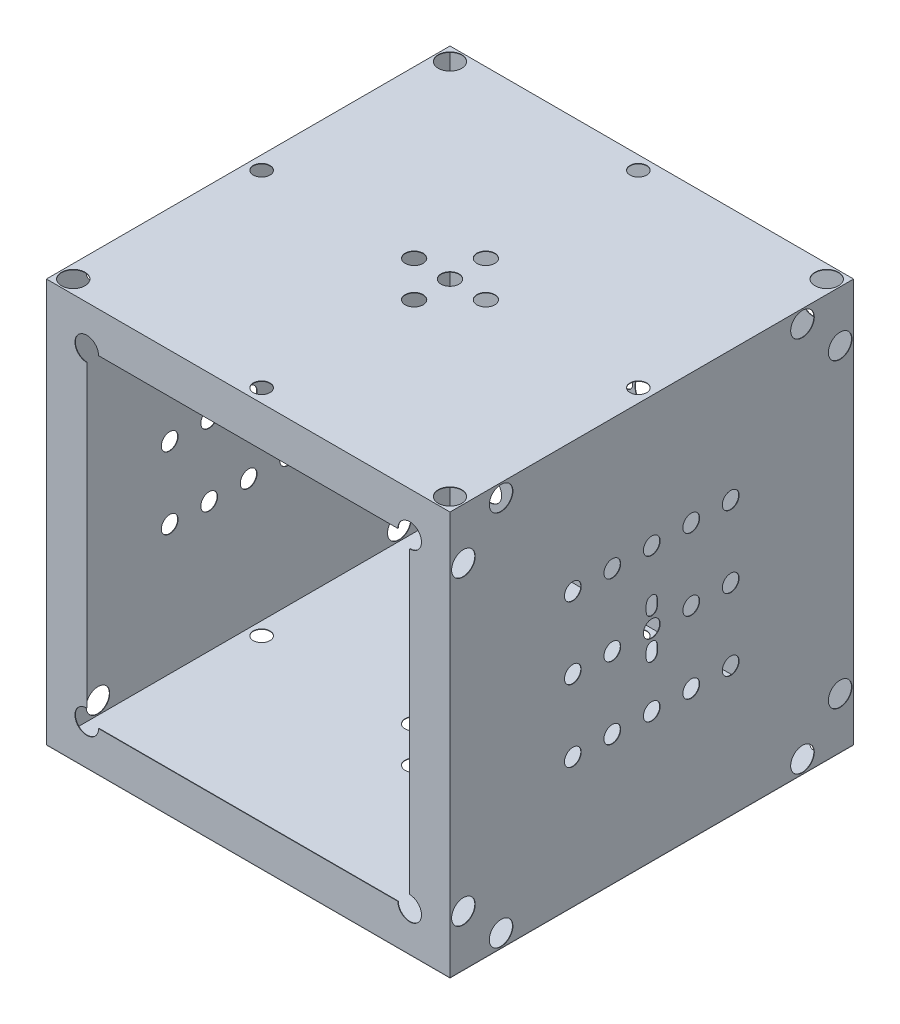
SolidWorks part; units mm, degrees
ref_plane "Front" through (0, 0, 0) normal (0, 0, 1) x (1, 0, 0)
ref_plane "Top" through (0, 0, 0) normal (0, 1, 0) x (1, 0, 0)
ref_plane "Right" through (0, 0, 0) normal (1, 0, 0) x (0, 0, -1)
sketch "Sketch1" plane through (0, 0, 0) normal (0, 1, 0) x (1, 0, 0)
  line L1 (-1124.8, 1124.8) -> (1124.8, 1124.8)
  line L2 (-1124.8, 1124.8) -> (-1124.8, -1124.8)
  line L3 (-1124.8, -1124.8) -> (1124.8, -1124.8)
  line L4 (1124.8, 1124.8) -> (1124.8, -1124.8)
  line L5 (-1124.8, 1124.8) -> (1124.8, -1124.8) construction
  line L6 (-1124.8, -1124.8) -> (1124.8, 1124.8) construction
  point P0 (0, 0)
  dimension "D1" = 2249.6
  dimension "D2" = 2249.6
extrude "Boss-Extrude1" add sketch "Sketch1" along normal blind 2249.6
shell "Shell1" thickness 2.4 removed face at (0, 1124.8, 1124.8)
sketch "Sketch2" plane through (0, 0, 1124.8) normal (0, 0, 1) x (1, 0, 0)
  line L0 (0, 2249.6) -> (0, 0) construction
  line L1 (-1124.8, 2249.6) -> (1124.8, 2249.6)
  line L2 (-1124.8, 2249.6) -> (-1124.8, 0)
  line L3 (-1124.8, 0) -> (1124.8, 0)
  line L4 (1124.8, 2249.6) -> (1124.8, 0)
  line L5 (1124.8, 1124.8) -> (-1124.8, 1124.8) construction
  line L7 (-900, 2024.8) -> (900, 2024.8)
  line L8 (-900, 2024.8) -> (-900, 224.8)
  line L9 (-900, 224.8) -> (900, 224.8)
  line L10 (900, 2024.8) -> (900, 224.8)
  line L11 (-900, 2024.8) -> (900, 224.8) construction
  line L12 (-900, 224.8) -> (900, 2024.8) construction
  point P11 (0, 1124.8)
  dimension "D1" = 1800
  dimension "D2" = 1800
extrude "Boss-Extrude3" add sketch "Sketch2" against normal blind 2.4
sketch "Sketch3" plane through (0, 2249.6, 0) normal (0, 1, 0) x (1, 0, 0)
  line L0 (-1124.8, 0) -> (1124.8, 0) construction
  line L1 (-1124.8, 1124.8) -> (-1124.8, -1124.8) construction
  line L2 (1124.8, -1124.8) -> (1124.8, 1124.8) construction
  line L3 (0, 1124.8) -> (0, -1124.8) construction
  line L4 (1124.8, 1124.8) -> (-1124.8, 1124.8) construction
  line L5 (-1124.8, -1124.8) -> (1124.8, -1124.8) construction
  line L6 (-1124.8, 1124.8) -> (0, 0) construction
  line L7 (0, 0) -> (-200, 0) construction
  circle A0 centre (0, 0) radius 49.85
  circle A1 centre (-200, 0) radius 49.85
  circle A2 centre (-1050, 0) radius 46.75
  circle A3 centre (-1050, 1050) radius 65.8
  circle A4 centre (1050, 1050) radius 65.8
  circle A5 centre (200, 0) radius 49.85
  circle A6 centre (1050, 0) radius 46.75
  circle A7 centre (-1050, -1050) radius 65.8
  circle A8 centre (0, -1050) radius 46.75
  circle A9 centre (0, -200) radius 49.85
  circle A10 centre (0, 200) radius 49.85
  circle A11 centre (0, 1050) radius 46.75
  circle A12 centre (1050, -1050) radius 65.8
  dimension "D1" = 99.7
  dimension "D4" = 93.5
  dimension "D6" = 131.6
  dimension "D3" = 200
  dimension "D5" = 1050
  dimension "D7" = 1050
  dimension "D2" = 2
extrude "Cut-Extrude1" cut sketch "Sketch3" against normal through all
sketch "Sketch4" plane through (-1124.8, 0, 0) normal (-1, 0, 0) x (0, 0, 1)
  line L0 (0, 2249.6) -> (0, 0) construction
  line L1 (-1124.8, 2249.6) -> (1124.8, 2249.6) construction
  line L2 (-1124.8, 1124.8) -> (1124.8, 1124.8) construction
  line L3 (-1124.8, 2249.6) -> (-1124.8, 0) construction
  line L4 (1124.8, 2249.6) -> (1124.8, 0) construction
  line L5 (-1124.8, 2249.6) -> (0, 1124.8) construction
  line L6 (0, 1124.8) -> (-220, 1124.8) construction
  line L7 (0, 1124.8) -> (0, 1524.8) construction
  line L8 (-440, 1124.8) -> (-440, 1524.8) construction
  line L9 (0, 1254.8) -> (0, 1217.3) construction
  line L10 (30.9, 1254.8) -> (30.9, 1217.3)
  line L11 (-30.9, 1254.8) -> (-30.9, 1217.3)
  line L12 (0, 994.8) -> (0, 1032.3) construction
  line L13 (30.9, 994.8) -> (30.9, 1032.3)
  line L14 (-30.9, 994.8) -> (-30.9, 1032.3)
  circle A0 centre (0, 1124.8) radius 46.75
  circle A1 centre (-220, 1124.8) radius 46.75
  circle A2 centre (-440, 1124.8) radius 46.75
  circle A6 centre (-440, 1524.8) radius 46.75 [skipped]
  circle A7 centre (-220, 1524.8) radius 46.75 [skipped]
  circle A8 centre (0, 1524.8) radius 46.75 [skipped]
  circle A9 centre (220, 1124.8) radius 46.75
  circle A10 centre (440, 1124.8) radius 46.75
  circle A11 centre (-440, 1524.8) radius 46.75
  circle A12 centre (-220, 1524.8) radius 46.75
  circle A13 centre (0, 1524.8) radius 46.75
  circle A14 centre (220, 1524.8) radius 46.75
  circle A15 centre (440, 1524.8) radius 46.75
  circle A16 centre (440, 724.8) radius 46.75
  circle A17 centre (220, 724.8) radius 46.75
  circle A18 centre (0, 724.8) radius 46.75
  circle A19 centre (-220, 724.8) radius 46.75
  circle A20 centre (-440, 724.8) radius 46.75
  arc A21 (30.9, 1254.8) -> (-30.9, 1254.8) centre (0, 1254.8) ccw
  arc A22 (-30.9, 1217.3) -> (30.9, 1217.3) centre (0, 1217.3) ccw
  arc A23 (30.9, 994.8) -> (-30.9, 994.8) centre (0, 994.8) cw
  arc A24 (-30.9, 1032.3) -> (30.9, 1032.3) centre (0, 1032.3) cw
  circle A25 centre (-840, 2174.8) radius 65.8
  circle A26 centre (-1050, 1964.8) radius 65.8
  circle A27 centre (1050, 1964.8) radius 65.8
  circle A28 centre (840, 2174.8) radius 65.8
  circle A29 centre (1050, 284.8) radius 65.8
  circle A30 centre (840, 74.8) radius 65.8
  circle A31 centre (-840, 74.8) radius 65.8
  circle A32 centre (-1050, 284.8) radius 65.8
  point P55 (0, 1236.05)
  point P62 (0, 1013.55)
  dimension "D1" = 93.5
  dimension "D8" = 30.9
  dimension "D11" = 131.6
  dimension "D4" = 220
  dimension "D5" = 400
  dimension "D7" = 400
  dimension "D9" = 92.5
  dimension "D10" = 37.5
  dimension "D12" = 840
  dimension "D13" = 1050
  dimension "D2" = 3
  dimension "D3" = 2
  dimension "D6" = 2
extrude "Cut-Extrude2" cut sketch "Sketch4" against normal through all
sketch "Sketch5" plane through (0, 0, -1124.8) normal (0, 0, -1) x (-1, 0, 0)
  line L0 (0, 2249.6) -> (0, 0) construction
  line L1 (-1124.8, 2249.6) -> (1124.8, 2249.6) construction
  line L2 (-1124.8, 1124.8) -> (1124.8, 1124.8) construction
  line L3 (-1124.8, 2249.6) -> (-1124.8, 0) construction
  line L4 (1124.8, 2249.6) -> (1124.8, 0) construction
  line L5 (0, 1124.8) -> (-1124.8, 2249.6) construction
  circle A0 centre (0, 1124.8) radius 91.2
  circle A1 centre (0, 1264.8) radius 35.635
  circle A2 centre (0, 984.8) radius 35.635
  circle A3 centre (140, 1124.8) radius 35.635
  circle A4 centre (-140, 1124.8) radius 35.635
  circle A5 centre (-222, 1506.8) radius 91.2
  circle A6 centre (222, 742.8) radius 91.2
  circle A7 centre (-900, 2024.8) radius 65.8
  circle A8 centre (900, 2024.8) radius 65.8
  circle A9 centre (900, 224.8) radius 65.8
  circle A10 centre (-900, 224.8) radius 65.8
  dimension "D1" = 182.4
  dimension "D2" = 71.27
  dimension "D4" = 182.4
  dimension "D7" = 182.4
  dimension "D10" = 131.6
  dimension "D3" = 140
  dimension "D5" = 222
  dimension "D6" = 382
  dimension "D8" = 222
  dimension "D9" = 382
  dimension "D11" = 900
extrude "Cut-Extrude3" cut sketch "Sketch5" against normal through all
split "Split1" bodies to split 108 resulting bodies 109 110 split by face at (0, 2.4, 1096.75)
